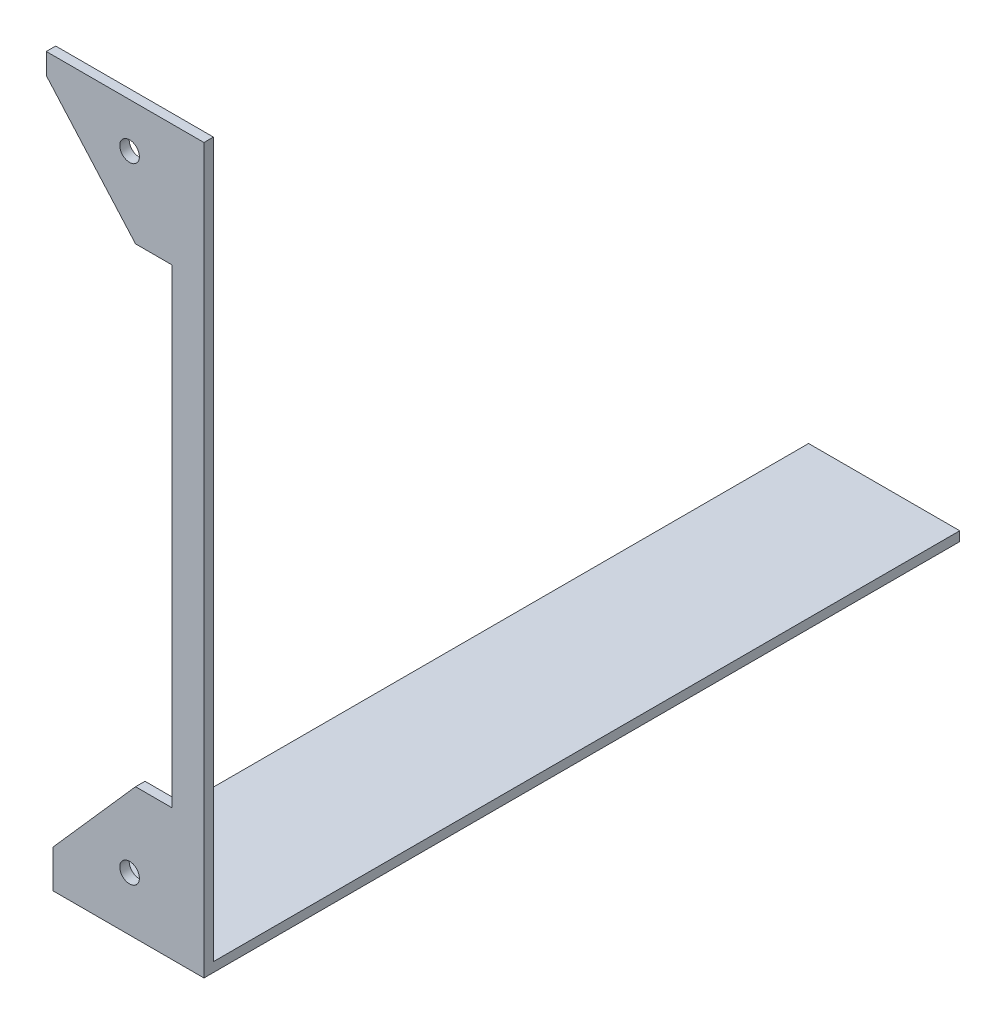
SolidWorks part; units mm, degrees
ref_plane "Front Plane" through (0, 0, 0) normal (0, 0, 1) x (1, 0, 0)
ref_plane "Top Plane" through (0, 0, 0) normal (0, 1, 0) x (1, 0, 0)
ref_plane "Right Plane" through (0, 0, 0) normal (1, 0, 0) x (0, 0, -1)
sketch "Sketch1" plane through (0, 0, 0) normal (0, 0, 1) x (1, 0, 0)
  line L0 (-250, 120) -> (0, 120) construction
  line L1 (0, 118) -> (0, 2) construction
  line L2 (0, 0) -> (-250, 0) construction
  line L3 (-26.5, 116.5) -> (-11.5, 99.5) construction
  line L4 (-11.5, 99.5) -> (-5.4, 99.5) construction
  line L5 (-5.4, 99.5) -> (-5.4, 20.5) construction
  line L6 (-11.5, 20.5) -> (-26.5, 3.5) construction
  line L7 (-5.4, 20.5) -> (-11.5, 20.5) construction
  line L8 (-26.5, 120) -> (0, 120)
  line L9 (0, 120) -> (0, 0)
  line L10 (0, 0) -> (-26.5, 0)
  line L11 (-26.5, 116.5) -> (-11.5, 99.5)
  line L12 (-11.5, 99.5) -> (-5.4, 99.5)
  line L13 (-5.4, 99.5) -> (-5.4, 20.5)
  line L14 (-11.5, 20.5) -> (-26.5, 3.5)
  line L15 (-5.4, 20.5) -> (-11.5, 20.5)
  line L16 (-26.5, 3.5) -> (-26.5, 0)
  line L17 (-26.5, 116.5) -> (-26.5, 120)
  line L18 (-25.4, 4.7467) -> (-25.4, 0)
  arc A0 (-14.15, 112.5) -> (-10.85, 112.5) centre (-12.5, 112.5) ccw construction
  arc A1 (-10.85, 112.5) -> (-14.15, 112.5) centre (-12.5, 112.5) ccw construction
  arc A2 (-14.15, 7.5) -> (-10.85, 7.5) centre (-12.5, 7.5) ccw construction
  arc A3 (-10.85, 7.5) -> (-14.15, 7.5) centre (-12.5, 7.5) ccw construction
  arc A4 (-14.15, 112.5) -> (-10.85, 112.5) centre (-12.5, 112.5) ccw
  arc A5 (-10.85, 112.5) -> (-14.15, 112.5) centre (-12.5, 112.5) ccw
  arc A6 (-14.15, 7.5) -> (-10.85, 7.5) centre (-12.5, 7.5) ccw
  arc A7 (-10.85, 7.5) -> (-14.15, 7.5) centre (-12.5, 7.5) ccw
  dimension "D1" = 25.4
extrude "Boss-Extrude1" add sketch "Sketch1" along normal blind 1.5875 contours L14 L18 L10 L9 L8 L17 L11 L12 L13 L15 A7 A6 A5 A4 region at (-13.25, 118.7711, 0)
sketch "Sketch2" plane through (0, 0, 0) normal (0, 1, 0) x (1, 0, 0)
  line L0 (0, -1.5875) -> (0, 125.4125)
  line L1 (0, 125.4125) -> (-25.4, 125.4125)
  line L2 (-25.4, 125.4125) -> (-25.4, -1.5875)
  line L4 (0, -1.5875) -> (-25.4, -1.5875) construction
  line L5 (0, -1.5875) -> (-25.4, -1.5875)
  point P4 (0, 0)
  point P8 (0, 0)
  point P9 (-25.7909, -1.5875)
  dimension "D1" = 127
extrude "Boss-Extrude2" add sketch "Sketch2" against normal blind 1.5875
